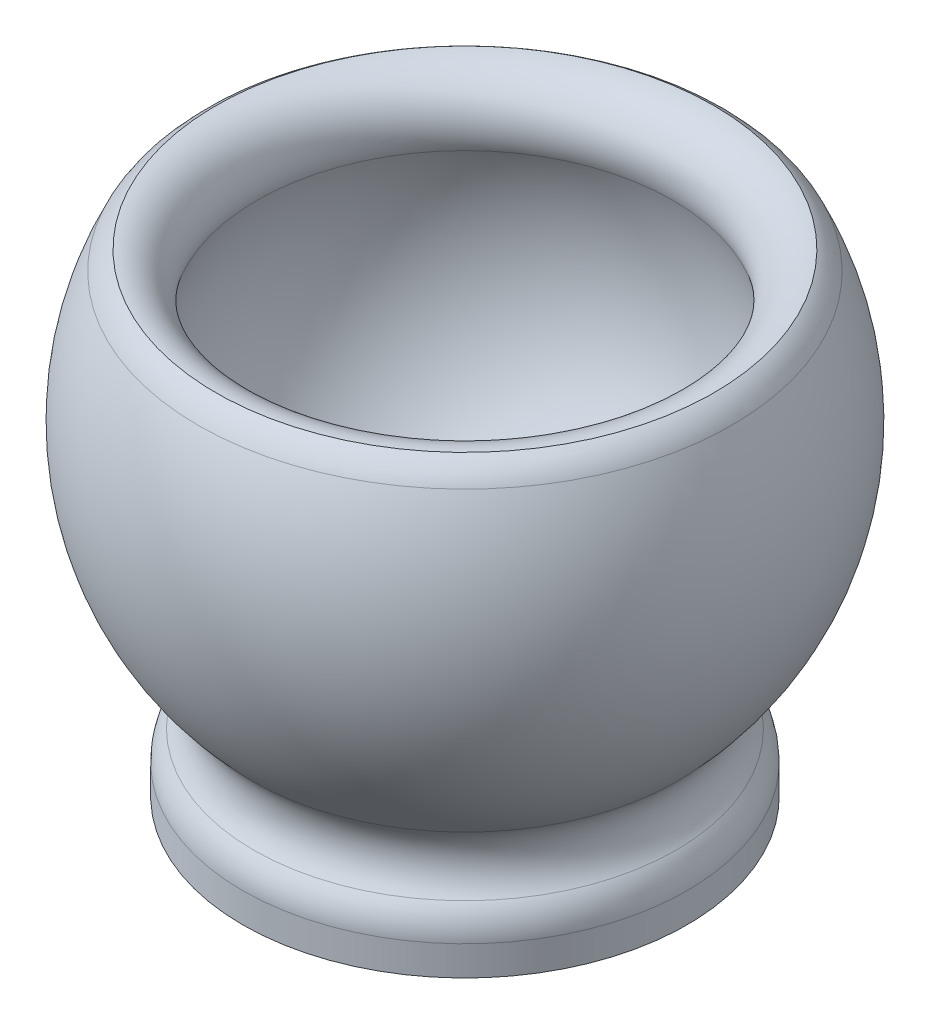
SolidWorks part; units mm, degrees
ref_plane "前视基准面" through (0, 0, 0) normal (0, 0, 1) x (1, 0, 0)
ref_plane "上视基准面" through (0, 0, 0) normal (0, 1, 0) x (1, 0, 0)
ref_plane "右视基准面" through (0, 0, 0) normal (1, 0, 0) x (0, 0, -1)
other "Configuration Table"
sketch "草图1" plane through (0, 0, 0) normal (0, 1, 0) x (1, 0, 0)
  line L0 (-24.0835, 0) -> (25.1351, 0) construction
  line L1 (-15.2, 0) -> (-20, 0)
  line L2 (20, 0) -> (15.2, 0)
  arc A0 (-20, 0) -> (20, 0) centre (0, 0) ccw
  arc A1 (-15.2, 0) -> (15.2, 0) centre (0, 0) ccw
  circle A3 centre (0, 0) radius 20 construction
  circle A4 centre (0, 0) radius 15.2 construction
  point P1 (15, 0)
  point P7 (19.1261, 5.8474)
  dimension "D1" = 40
  dimension "D2" = 4.8
revolve "旋转5" add sketch "草图1" angle 360 about L0
sketch "草图2" plane through (0, 0, 0) normal (1, 0, 0) x (0, 0, -1)
  line L1 (-37.1806, 35) -> (36.2954, 35)
  line L2 (-37.1806, 35) -> (-37.1806, 10)
  line L3 (-37.1806, 10) -> (36.2954, 10)
  line L4 (36.2954, 35) -> (36.2954, 10)
  dimension "D1" = 35
  dimension "D2" = 10
extrude "切除-拉伸1" cut sketch "草图2" against normal through all and the other way through all
fillet "圆角1" radius 3 1 edges at (0, 10, -11.4473)
ref_plane "基准面1" through (0, -22, 0) normal (0, 1, 0) x (1, 0, 0)
sketch "草图3" plane through (0, -22, 0) normal (0, 1, 0) x (1, 0, 0)
  circle A0 centre (0, 0) radius 6
  dimension "D1" = 12
extrude "凸台-拉伸1" add sketch "草图3" along normal up to next
sketch "草图4" plane through (0, -22, 0) normal (0, -1, 0) x (-1, 0, 0)
  circle A0 centre (0, 0) radius 15
  dimension "D1" = 30
extrude "凸台-拉伸2" add sketch "草图4" against normal blind 5
fillet "圆角3" radius 3 1 edges at (0, 10, -17.3205)
fillet "圆角4" radius 3 1 edges at (0, -17, -15)
fillet "圆角5" radius 3 1 edges at (0, -17, -10.5357)
